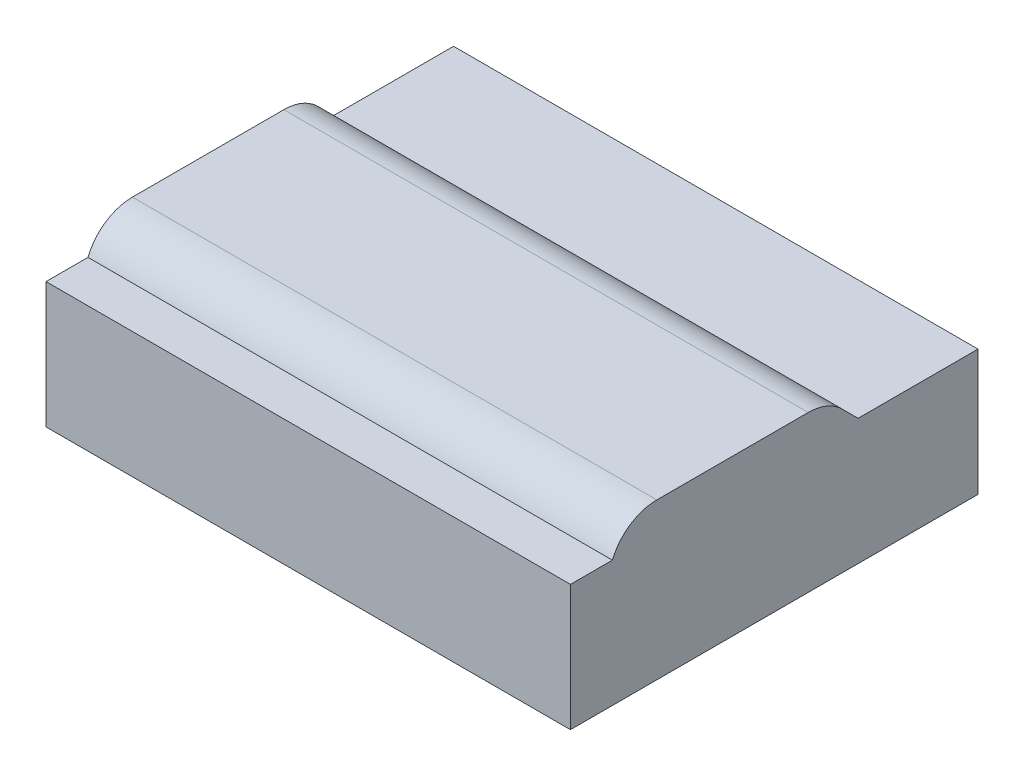
SolidWorks part; units mm, degrees
ref_plane "Front Plane" through (0, 0, 0) normal (0, 0, 1) x (1, 0, 0)
ref_plane "Top Plane" through (0, 0, 0) normal (0, 1, 0) x (1, 0, 0)
ref_plane "Right Plane" through (0, 0, 0) normal (1, 0, 0) x (0, 0, -1)
sketch "Sketch1" plane through (0, 0, 0) normal (0, 1, 0) x (1, 0, 0)
  line L1 (-437.5, 680) -> (437.5, 680)
  line L2 (-437.5, 680) -> (-437.5, 0)
  line L3 (-437.5, 0) -> (437.5, 0)
  line L4 (437.5, 680) -> (437.5, 0)
  point P4 (0, 680)
  dimension "D1" = 680
  dimension "D2" = 875
extrude "Boss-Extrude1" add sketch "Sketch1" against normal blind 210
sketch "Sketch3" plane through (-437.5, 0, 0) normal (-1, 0, 0) x (0, 0, 1)
  line L1 (-680, 0) -> (0, 0) construction
  line L2 (-70, 0) -> (-430, 0)
  line L3 (-70, 0) -> (-70, 50)
  line L4 (-70, 50) -> (-430, 50)
  line L5 (-430, 0) -> (-430, 50)
  line L6 (0, -210) -> (0, 0) construction
  line L7 (-430, 50) -> (-480, 0)
  line M1 (0, 0) -> (-680, 0)
  dimension "D2" = 70
  dimension "D1" = 50
  dimension "D3" = 360
  dimension "D4" = 50
extrude "Boss-Extrude2" add sketch "Sketch3" against normal up to surface (875 mm away) contours L5 L3 L4 M1 | L5 L7 M1 up to face at (437.5, -105, -340)
fillet "Fillet1" radius 80 2 edges at (0, 50, -70) (0, 50, -430)
sketch "Sketch4" plane through (0, 50, 0) normal (0, 1, 0) x (1, 0, 0)
  line L0 (-437.5, 270.5124) -> (437.5, 270.5124)
  line L1 (-437.5, 144.162) -> (-437.5, 396.8629) construction
  line L2 (437.5, 144.162) -> (437.5, 396.8629) construction
sketch3d "3DSketch1"
  line L0 (0, 50, -270.5124) -> (0, -210, -270.5124)
  line L1 (-437.5, 50, -270.5124) -> (437.5, 50, -270.5124) construction
  line L2 (437.5, 50, -270.5124) -> (-437.5, 50, -270.5124)
  line L3 (437.5, 50, -144.162) -> (437.5, 50, -396.8629) construction
  line L4 (-437.5, 50, -144.162) -> (-437.5, 50, -396.8629) construction
  line L5 (0, 50, -144.162) -> (0, 50, -396.8629)
  line L6 (-437.5, 50, -144.162) -> (437.5, 50, -144.162) construction
  line L7 (437.5, 50, -396.8629) -> (-437.5, 50, -396.8629) construction
